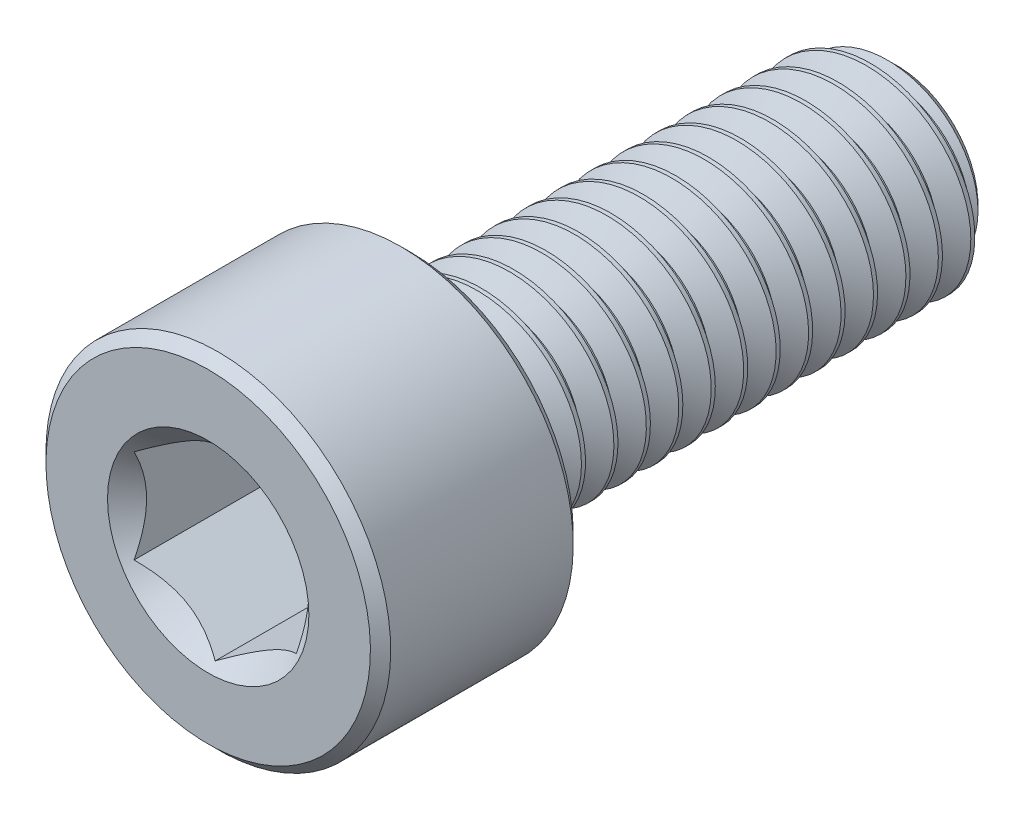
SolidWorks part; units mm, degrees
ref_plane "Front Plane" through (0, 0, 0) normal (0, 0, 1) x (1, 0, 0)
ref_plane "Top Plane" through (0, 0, 0) normal (0, 1, 0) x (1, 0, 0)
ref_plane "Right Plane" through (0, 0, 0) normal (1, 0, 0) x (0, 0, -1)
sketch "Sketch1" plane through (0, 0, 0) normal (1, 0, 0) x (0, 0, -1)
  line L0 (-8.5, 0) -> (8.5, 0) construction
  line L1 (8.5, 0) -> (8.5, 1.9804) construction
  line L2 (8.5, 1.9804) -> (7.9804, 2.5) construction
  line L3 (7.9804, 2.5) -> (7.9, 2.5) construction
  line L4 (7.9, 2.5) -> (-3.5, 2.5) construction
  line L5 (-3.5, 2.5) -> (-3.5, 4.25) construction
  line L6 (-3.5, 4.25) -> (-8.5, 4.25) construction
  line L7 (-8.5, 4.25) -> (-8.5, 0) construction
  line L8 (8.5, 1.9804) -> (8.5, 2.5) construction
  line L9 (8.45, 2.5866) -> (8.85, 1.8938) construction
  line L10 (8.85, 1.8938) -> (9.25, 2.5866) construction
  line L11 (9.25, 2.5866) -> (8.45, 2.5866) construction
  line L12 (8.85, 2.5866) -> (8.85, 2.5) construction
  line L13 (8.85, 1.8938) -> (8.85, 1.9804) construction
  line L14 (8.8, 1.9804) -> (8.9, 1.9804) construction
  line L15 (8.5, 2.5) -> (9.2, 2.5) construction
  line L16 (8.475, 2.5433) -> (9.225, 2.5433) construction
  line L17 (8.5, 0) -> (8.5, -2.5) construction
  line L18 (-3.75, 4.25) -> (-3.5, 4) construction
  line L19 (-8.25, 4.25) -> (-8.5, 4) construction
  line L20 (-3.5, 2.5) -> (-3.5, 0) construction
  line L21 (-3.5, 1.25) -> (0.5, 1.25) construction
  line L22 (0.5, 1.25) -> (4.5, 1.25) construction
  line L23 (4.5, 1.25) -> (8.5, 1.25) construction
  line L24 (0.5, 1.25) -> (0.5, 2.5) construction
  line L25 (0.5, 2.5) -> (0.5, 4.25) construction
  line L26 (4.5, 1.25) -> (4.5, 4.25) construction
  point P0 (-8.5, 2)
  point P3 (6.5, 2.5)
  point P4 (0, 0)
  point P18 (4.5, 2.5)
  point P22 (8.85, 1.9804)
  point P24 (7.9, 2.5)
  point P25 (8.85, 2.5)
  point P28 (8.85, 2.5433)
  point P29 (6.5, -2.5)
  point P30 (0.5, 2.5)
  point P31 (-6, 4.25)
  point P37 (-4.375, 4.25)
  point P38 (-8.125, 4.25)
  point P45 (0.5, 1.25)
  point P46 (4.5, 1.25)
  dimension "D2" = 0.1
  dimension "D7" = 0.25
  dimension "D8" = 0.25
  dimension "D9" = 0.25
  dimension "D10" = 0.125
  dimension "D11" = 0.625
  dimension "Drive Size" = 4
  dimension "Head Diameter" = 8.5
  dimension "Head Height" = 5
  dimension "Thread Pitch" = 0.8
  dimension "Thread Dia" = 5
  dimension "Length" = 12
  dimension "D12" = 0.6
  dimension "D4" = 2
  dimension "D3" = 45
sketch "Sketch2" plane through (0, 0, 0) normal (1, 0, 0) x (0, 0, -1)
  line L0 (-8.5, 0) -> (-8.5, 4)
  line L1 (-8.25, 4.25) -> (-3.75, 4.25)
  line L2 (-3.5, 4) -> (-3.5, 2.75)
  line L4 (7.9804, 2.5) -> (8.5, 1.9804)
  line L5 (8.5, 1.9804) -> (8.5, 0)
  line L6 (-3.5, 4.25) -> (-8.5, 4.25) construction
  line L7 (8.5, 0) -> (-8.5, 0)
  line L8 (-8.25, 4.25) -> (-8.5, 4) construction
  line L10 (-8.25, 4.25) -> (-8.5, 4)
  line L14 (-3.75, 4.25) -> (-3.5, 4) construction
  line L16 (-3.75, 4.25) -> (-3.5, 4)
  line L17 (-3.5, 2.5) -> (-3.5, 4.25) construction
  line L19 (-3.25, 2.5) -> (7.9804, 2.5)
  line L20 (7.9, 2.5) -> (-3.5, 2.5) construction
  arc A1 (-3.5, 2.75) -> (-3.25, 2.5) centre (-3.25, 2.75) ccw
  dimension "D3" = 0.25
revolve "Revolve1" add sketch "Sketch2" angle 360 about L7
sketch "Sketch3" plane through (0, 0, 8.5) normal (0, 0, 1) x (1, 0, 0)
  line L1 (2, -1.1547) -> (2, 1.1547)
  line L2 (2, 1.1547) -> (0, 2.3094)
  line L3 (0, 2.3094) -> (-2, 1.1547)
  line L4 (-2, 1.1547) -> (-2, -1.1547)
  line L5 (-2, -1.1547) -> (0, -2.3094)
  line L6 (0, -2.3094) -> (2, -1.1547)
  circle A0 centre (0, 0) radius 2 construction
  circle A1 centre (0, 0) radius 4.25 construction
  circle A2 centre (0, 0) radius 4.25 construction
  circle A3 centre (0, 0) radius 2.3094 construction
  point P13 (0, 0)
  dimension "D1" = 4.6188
extrude "Cut-Extrude1" cut sketch "Sketch3" against normal offset from surface (4 mm away) 1 up to face at (0, 4, 3.5)
sketch "Sketch4" plane through (0, 0, 8.5) normal (0, 0, 1) x (1, 0, 0)
  circle A0 centre (0, 0) radius 2.4826
  dimension "D1" = 4.9652
extrude "Cut-Extrude2" cut sketch "Sketch4" against normal up to vertex (2.5 mm away) draft 45 up to point (0, 4.25, 6)
sketch "Sketch11" plane through (0, 0, 0) normal (1, 0, 0) x (0, 0, -1)
  line L0 (-8.5, 0) -> (8.5, 0) construction
  line L1 (-8.5, 0) -> (8.5, 0) construction
  line L2 (-1.25, 0) -> (-1.25, 2.5) construction
  line L3 (7.9, 2.5) -> (-3.5, 2.5) construction
  line L4 (6.25, 0) -> (6.25, 2.5) construction
  line L6 (8.5, 1.9804) -> (8.5, 2.5) construction
  point P2 (-1.25, 0)
  point P3 (6.25, 0)
  dimension "D1" = 2.25
  dimension "D2" = 2.25
sketch "Sketch6" plane through (0, 0, -8.5) normal (0, 0, -1) x (-1, 0, 0)
  circle A0 centre (0, 0) radius 2.5
curve "Helix/Spiral1" pitch 0.8 height 12.8 radius 2.5 centre (0, 0, -8.5) axis (0, 0, 1) start towards (0, 1, 0)
sketch "Sketch10" plane through (0, 0, 0) normal (1, 0, 0) x (0, 0, -1)
  line L0 (-3.25, -4.25) -> (-3.25, 4.25)
  line L5 (-8.5, 0) -> (8.5, 0) construction
  line L6 (-3.25, 2.5) -> (-3.25, -2.5) construction
  point P3 (-3.25, 0)
split "Split1" trim tools "Sketch10" bodies to split 106 resulting bodies 114 115
sketch "Sketch7" plane through (0, 0, 0) normal (1, 0, 0) x (0, 0, -1)
  line L0 (8.475, 2.5433) -> (9.225, 2.5433)
  line L1 (9.225, 2.5433) -> (8.9, 1.9804)
  line L2 (8.9, 1.9804) -> (8.8, 1.9804)
  line L3 (8.8, 1.9804) -> (8.475, 2.5433)
sweep "Cut-Sweep1" cut profiles "Sketch7" path "Helix/Spiral1" align with end faces yes
sketch "Sketch8" plane through (0, 0, 0) normal (1, 0, 0) x (0, 0, -1)
  line L0 (-3.5, 0) -> (-3.5, 2.5)
  line L1 (-3.25, -2.5) -> (-3.25, 2.5) construction
  line L2 (-3.5, 2.5) -> (-3.25, 2.5)
  line L4 (-3.25, 2.5) -> (-1.8066, 0)
  line L5 (-1.8066, 0) -> (-3.5, 0)
  line L6 (7.9, 2.5) -> (-3.5, 2.5) construction
  line L7 (-8.5, 0) -> (8.5, 0) construction
  dimension "D1" = 60
revolve "Revolve2" add sketch "Sketch8" angle 360 about L5
equation "\"D2@Sketch1\" = \"Thread Pitch@Sketch1\" / 8"
equation "\"D4@Helix/Spiral1\" = \"Thread Pitch@Sketch1\""
equation "\"D7@Sketch1\" = \"Head Height@Sketch1\" * .05"
equation "\"D8@Sketch1\"=\"D7@Sketch1\""
equation "\"D9@Sketch1\"=\"D7@Sketch1\""
equation "\"D10@Sketch1\"=\"D7@Sketch1\"/2"
equation "\"D11@Sketch1\"=\"D10@Sketch1\"*5"
equation "\"D4@Sketch1\"=\"Thread Pitch@Sketch1\"*2.5"
equation "\"D12@Sketch1\"=\"Thread Pitch@Sketch1\"*.75"
equation "\"D3@Helix/Spiral1\"=\"Length@Sketch1\"+\"Thread Pitch@Sketch1\""
equation "\"D3@Sketch2\"=\"Thread Dia@Sketch1\"*0.05"
equation "\"D1@Sketch11\"=\"Length@Sketch1\"*0.1875"
equation "\"D2@Sketch11\"=\"D1@Sketch11\""
equation "\"D1@Sketch4\"=\"D1@Sketch3\"*1.075"
